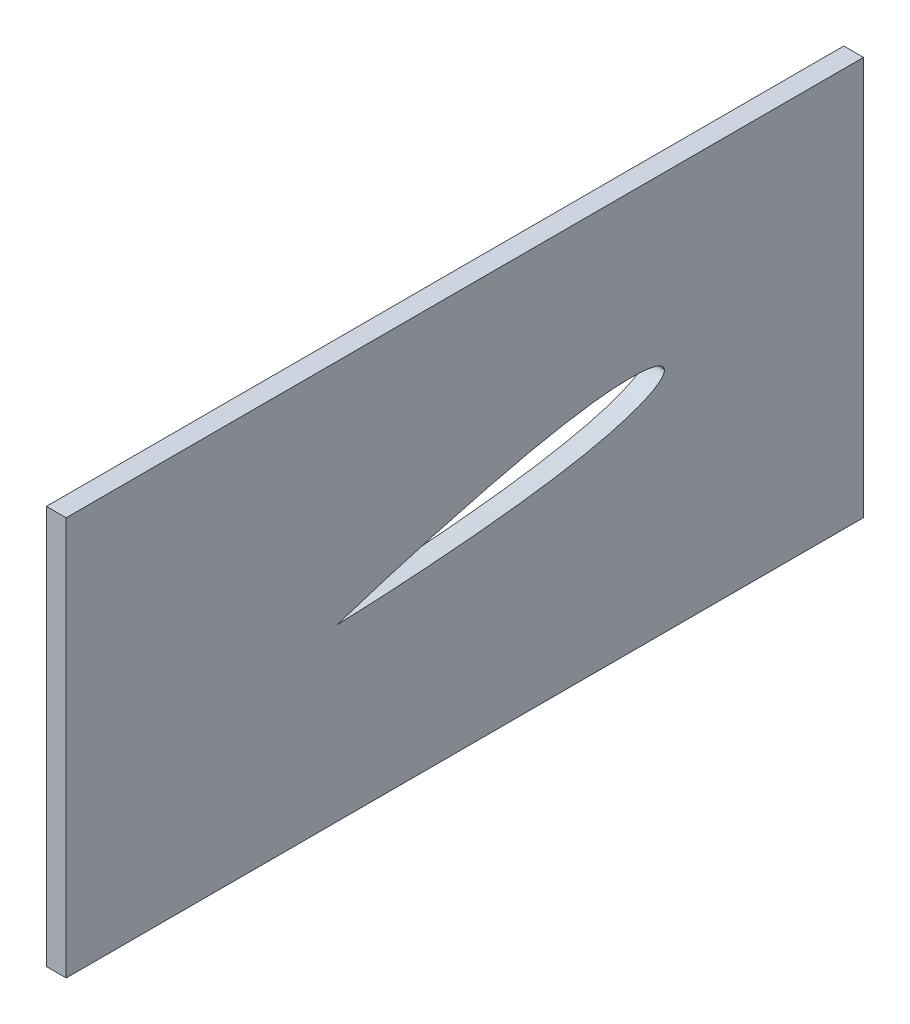
SolidWorks part; units mm, degrees
material "Custom Plastic"
ref_plane "Front Plane" through (0, 0, 0) normal (0, 0, 1) x (1, 0, 0)
ref_plane "Top Plane" through (0, 0, 0) normal (0, 1, 0) x (1, 0, 0)
ref_plane "Right Plane" through (0, 0, 0) normal (1, 0, 0) x (0, 0, -1)
other "Configuration Table"
sketch "Sketch1" plane through (0, 0, 0) normal (1, 0, 0) x (0, 0, -1)
  spline S0 degree 4 poles (0, 0) (0, 0.0009) (0.0001, 0.0028) (0.0009, 0.006) (0.0029, 0.0097) (0.0068, 0.0145) (0.0126, 0.0192) (0.0211, 0.0244) (0.0349, 0.0306) (0.0554, 0.0375) (0.0898, 0.0455) (0.1398, 0.0529) (0.2034, 0.0579) (0.2766, 0.06) (0.3533, 0.0592) (0.4293, 0.0565) (0.5064, 0.052) (0.5813, 0.0466) (0.6596, 0.0397) (0.7322, 0.0327) (0.814, 0.0237) (0.8804, 0.0161) (0.9794, 0.0031) (1.0221, -0.003) (1.0781, -0.0115) (1.0995, -0.0151) knots 0 0 0 0 0 0.003159 0.007001 0.011626 0.014779 0.024842 0.033543 0.04731 0.068441 0.102186 0.159339 0.227558 0.295777 0.363996 0.432215 0.500435 0.568654 0.636873 0.705092 0.773311 0.84153 0.909749 1 1 1 1 1 construction
  spline S1 degree 4 poles (0, 0) (0, 0.0009) (0.0001, 0.0028) (0.0009, 0.006) (0.0029, 0.0097) (0.0068, 0.0145) (0.0126, 0.0192) (0.0211, 0.0244) (0.0349, 0.0306) (0.0554, 0.0375) (0.0898, 0.0455) (0.1398, 0.0529) (0.2034, 0.0579) (0.2766, 0.06) (0.3533, 0.0592) (0.4293, 0.0565) (0.5064, 0.052) (0.5813, 0.0466) (0.6596, 0.0397) (0.7322, 0.0327) (0.814, 0.0237) (0.8804, 0.0161) (0.9491, 0.0071) (0.9828, 0.0024) (1, 0) knots 0 0 0 0 0 0.003159 0.007001 0.011626 0.014779 0.024842 0.033543 0.04731 0.068441 0.102186 0.159339 0.227558 0.295777 0.363996 0.432215 0.500435 0.568654 0.636873 0.705092 0.773311 0.84153 0.909749 0.909749 0.909749 0.909749 0.909749
  spline S2 degree 4 poles (0, 0) (0, -0.0009) (0.0001, -0.0028) (0.0009, -0.006) (0.0029, -0.0097) (0.0068, -0.0145) (0.0126, -0.0192) (0.0211, -0.0244) (0.0349, -0.0306) (0.0554, -0.0375) (0.0898, -0.0455) (0.1398, -0.0529) (0.2034, -0.0579) (0.2766, -0.06) (0.3533, -0.0592) (0.4293, -0.0565) (0.5064, -0.052) (0.5813, -0.0466) (0.6596, -0.0397) (0.7322, -0.0327) (0.814, -0.0237) (0.8804, -0.0161) (0.9491, -0.0071) (0.9828, -0.0024) (1, 0) knots 0 0 0 0 0 0.003159 0.007001 0.011626 0.014779 0.024842 0.033543 0.04731 0.068441 0.102186 0.159339 0.227558 0.295777 0.363996 0.432215 0.500435 0.568654 0.636873 0.705092 0.773311 0.84153 0.909749 0.909749 0.909749 0.909749 0.909749
  point P0 (0, 0)
extrude "Boss-Extrude1" add sketch "Sketch1" along normal blind 0.06 contours S1 S2
scale "Scale1" bodies to scale 133 scale about origin uniform scaling yes scale factor 1000
mirror "Mirror2" about plane through (0, 0, 0) normal (0, 0, 1) of bodies 134
delete or keep bodies "Body-Delete/Keep 1" type delete bodies bodies 134
ref_axis "Axis1" through (129.9188, 0, 0) along (-1, 0, 0)
move or copy body "Body-Move/Copy1" bodies to move or copy 135 copy no rotation origin (0, 0, 0) rotation axis (1, 0, 0) rotation angle 10 parameters "Angle Around Edge"=350
sketch "Sketch2" plane through (0, 0, 0) normal (1, 0, 0) x (0, 0, -1)
  line L0 (0, 0) -> (-984.8078, -173.6482) construction
  line L1 (600, 513.1759) -> (-1800, 513.1759)
  line L2 (600, 513.1759) -> (600, -686.8241)
  line L3 (600, -686.8241) -> (-1800, -686.8241)
  line L4 (-1800, 513.1759) -> (-1800, -686.8241)
  point P4 (-492.4039, -86.8241)
  dimension "D1" = 600
  dimension "D2" = 1800
  dimension "D3" = 1200
  dimension "D4" = 600
extrude "Boss-Extrude2" add sketch "Sketch2" along normal up to surface (60 mm away) separate body up to face at (60, 0, 0)
combine bodies "Combine1" operation type subtract main body 137 bodies to subtract 136
other "Move Face1" flip direction yes face at (30, -86.8241, 1800) face at (30, -686.8241, 600) face at (60, 0, 0) face at (30, -86.8241, -600) face at (30, 513.1759, 600) face at (0, 0, 0) offset 0.3 parameters "D1"=0.3
